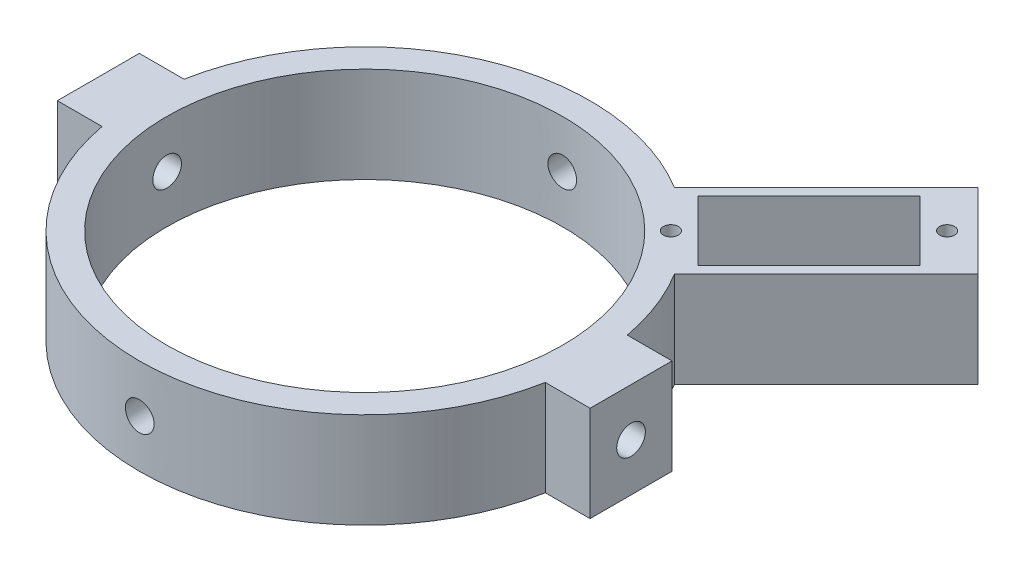
SolidWorks part; units mm, degrees
ref_plane "Front Plane" through (0, 0, 0) normal (0, 0, 1) x (1, 0, 0)
ref_plane "Top Plane" through (0, 0, 0) normal (0, 1, 0) x (1, 0, 0)
ref_plane "Right Plane" through (0, 0, 0) normal (1, 0, 0) x (0, 0, -1)
sketch "Sketch1" plane through (0, 0, 0) normal (0, 1, 0) x (1, 0, 0)
  circle A0 centre (0, 0) radius 29
  circle A1 centre (0, 0) radius 33
  dimension "D1" = 58
  dimension "D2" = 66
extrude "Boss-Extrude1" add sketch "Sketch1" along normal mid plane 14
sketch "Sketch2" plane through (0, 0, 0) normal (0, 1, 0) x (1, 0, 0)
  line L9 (29, -6) -> (39, -6)
  line L10 (29, -6) -> (29, 6)
  line L11 (29, 6) -> (39, 6)
  line L12 (39, -6) -> (39, 6)
  line L13 (29, -6) -> (39, 6) construction
  line L14 (29, 6) -> (39, -6) construction
  line L15 (-29, -6) -> (-39, -6)
  line L16 (-29, -6) -> (-29, 6)
  line L17 (-29, 6) -> (-39, 6)
  line L18 (-39, -6) -> (-39, 6)
  line L19 (-29, -6) -> (-39, 6) construction
  line L20 (-29, 6) -> (-39, -6) construction
  circle A1 centre (0, 0) radius 29 construction
  point P0 (34, 0)
  point P7 (0, 0)
  point P8 (-34, 0)
  dimension "D1" = 12
  dimension "D2" = 10
  dimension "D3" = 10
  dimension "D4" = 12
extrude "Boss-Extrude2" add sketch "Sketch2" along normal mid plane 14
sketch "Sketch5" plane through (-39, 0, 0) normal (-1, 0, 0) x (0, 0, 1)
  circle A0 centre (0, 0) radius 2.1
  dimension "D1" = 4.2
extrude "Cut-Extrude1" cut sketch "Sketch5" against normal through all
sketch "Sketch7" plane through (0, 0, 0) normal (0, 0, 1) x (1, 0, 0)
  circle A0 centre (0, 0) radius 2.1
  dimension "D1" = 4.2
extrude "Cut-Extrude4" cut sketch "Sketch7" against normal blind 46.5 and the other way blind 36.5 contours A0
sketch "Sketch11" plane through (0, 0, 0) normal (0, 1, 0) x (1, 0, 0)
  line L0 (3.532, 3.532) -> (15.2298, 15.2298) construction
  line L1 (39.4212, 50.3814) -> (50.3814, 39.4212)
  line L2 (39.4212, 50.3814) -> (15.026, 25.9862)
  line L3 (15.026, 25.9862) -> (25.9862, 15.026)
  line L4 (50.3814, 39.4212) -> (25.9862, 15.026)
  line L5 (39.4212, 50.3814) -> (25.9862, 15.026) construction
  line L6 (15.026, 25.9862) -> (50.3814, 39.4212) construction
  circle A0 centre (0, 0) radius 29 construction
  point P0 (32.7037, 32.7037)
  dimension "D2" = 34.5
  dimension "D1" = 15.5
extrude "Boss-Extrude4" add sketch "Sketch11" along normal mid plane 14
sketch "Sketch12" plane through (0, 7, 0) normal (0, 1, 0) x (1, 0, 0)
  line L0 (50.3814, 39.4212) -> (39.4212, 50.3814) construction
  line L1 (28.8146, 19.9758) -> (19.9758, 28.8146)
  line L2 (28.8146, 19.9758) -> (45.0781, 36.2392)
  line L3 (45.0781, 36.2392) -> (36.2392, 45.0781)
  line L4 (19.9758, 28.8146) -> (36.2392, 45.0781)
  line L5 (28.8146, 19.9758) -> (36.2392, 45.0781) construction
  line L6 (45.0781, 36.2392) -> (19.9758, 28.8146) construction
  line L7 (28.162, 17.2018) -> (50.3814, 39.4212) construction
  line L9 (39.4212, 50.3814) -> (17.2018, 28.162) construction
  line L10 (31.4685, 31.4685) -> (26.5252, 26.5252) construction
  circle A1 centre (22.4153, 22.4153) radius 1.1
  circle A2 centre (42.6385, 42.6385) radius 1.1
  point P0 (32.5269, 32.5269)
  point P15 (24.3952, 24.3952)
  dimension "D5" = 2.2
  dimension "D7" = 2.2
  dimension "D1" = 34.5
  dimension "D2" = 6
  dimension "D3" = 1.5
  dimension "D4" = 1.5
  dimension "D6" = 2.8
  dimension "D8" = 2.8
  dimension "D9" = 23
extrude "Cut-Extrude6" cut sketch "Sketch12" against normal through all
sketch "Sketch13" plane through (24.3952, 0, -24.3952) normal (0.7071, 0, -0.7071) x (-0.7071, 0, -0.7071)
  circle A0 centre (0, 0) radius 2.1
  dimension "D1" = 4.2
